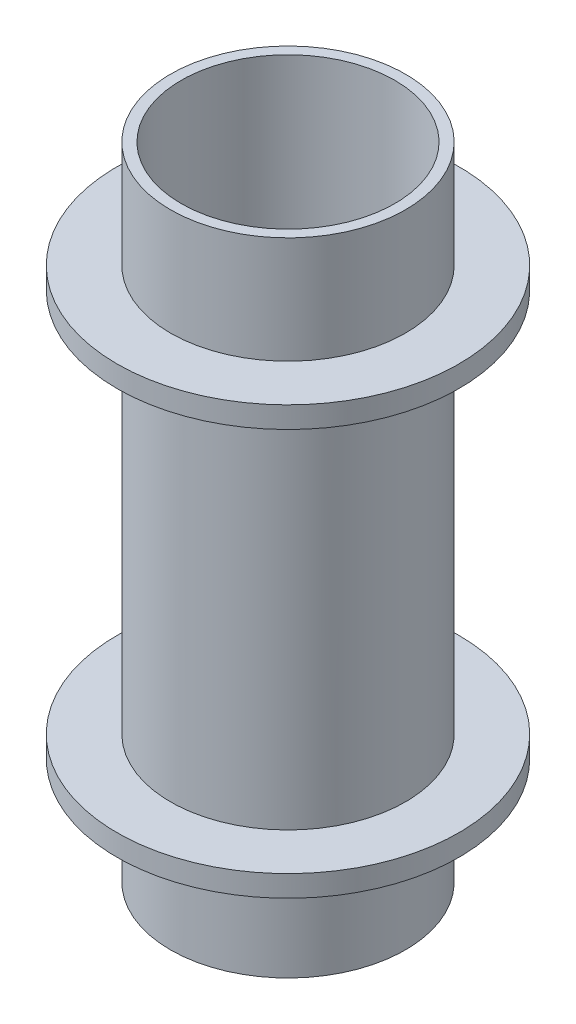
SolidWorks part; units mm, degrees
ref_plane "Спереди" through (0, 0, 0) normal (0, 0, 1) x (1, 0, 0)
ref_plane "Сверху" through (0, 0, 0) normal (0, 1, 0) x (1, 0, 0)
ref_plane "Справа" through (0, 0, 0) normal (1, 0, 0) x (0, 0, -1)
other "Центр тяжести"
sketch "Эскиз1" plane through (0, 0, 0) normal (0, 1, 0) x (1, 0, 0)
  circle A0 centre (0, 0) radius 10
  circle A1 centre (0, 0) radius 11
  dimension "D1" = 20
  dimension "D2" = 22
extrude "Бобышка-Вытянуть1" add sketch "Эскиз1" along normal blind 60
sketch "Эскиз2" plane through (0, 60, 0) normal (0, 1, 0) x (1, 0, 0)
  circle A1 centre (0, 0) radius 16
  circle A3 centre (0, 0) radius 11
  dimension "D1" = 32
extrude "Бобышка-Вытянуть3" add sketch "Эскиз2" against normal blind 2 from offset 10 offset against normal yes
sketch "Эскиз3" plane through (0, 0, 0) normal (0, -1, 0) x (1, 0, 0)
  circle A0 centre (0, 0) radius 11
  circle A1 centre (0, 0) radius 16
extrude "Бобышка-Вытянуть4" add sketch "Эскиз3" against normal blind 2 from offset 10 offset against normal yes
